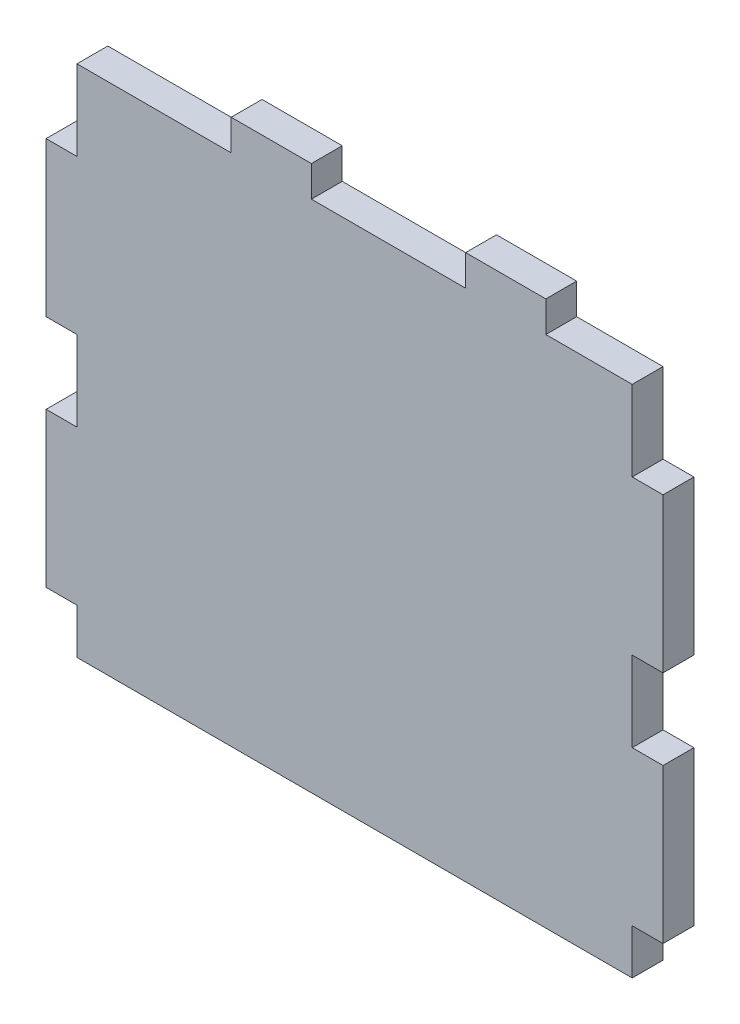
SolidWorks part; units mm, degrees
material "Oak"
ref_plane "Front Plane" through (0, 0, 0) normal (0, 0, 1) x (1, 0, 0)
ref_plane "Top Plane" through (0, 0, 0) normal (0, 1, 0) x (1, 0, 0)
ref_plane "Right Plane" through (0, 0, 0) normal (1, 0, 0) x (0, 0, -1)
sketch "Sketch1" plane through (0, 0, 0) normal (0, 0, 1) x (1, 0, 0)
  line L1 (-40.9935, 16.542) -> (19.0065, 16.542)
  line L2 (-40.9935, 16.542) -> (-40.9935, -33.458)
  line L3 (-40.9935, -33.458) -> (19.0065, -33.458)
  line L4 (19.0065, 16.542) -> (19.0065, -33.458)
  dimension "D1" = 50
  dimension "D2" = 60
extrude "Boss-Extrude1" add sketch "Sketch1" along normal blind 3
sketch "Sketch2" plane through (0, 0, 3) normal (0, 0, 1) x (1, 0, 0)
  line L12 (-40.9935, 16.542) -> (-37.9935, 16.542)
  line L13 (-40.9935, 16.542) -> (-40.9935, 8.742)
  line L14 (-40.9935, 8.742) -> (-37.9935, 8.742)
  line L15 (-37.9935, 16.542) -> (-37.9935, 8.742)
  dimension "D1" = 7.8
  dimension "D2" = 3
extrude "Cut-Extrude1" cut sketch "Sketch2" against normal through all
pattern_linear "LPattern1" count 3 spacing 22.8 along (0, -1, 0) of "Cut-Extrude1"
sketch "Sketch3" plane through (0, 0, 3) normal (0, 0, 1) x (1, 0, 0)
  line L0 (19.0065, 16.542) -> (-37.9935, 16.542) construction
  line L1 (16.0065, 16.542) -> (19.0065, 16.542)
  line L2 (16.0065, 16.542) -> (16.0065, 8.742)
  line L3 (16.0065, 8.742) -> (19.0065, 8.742)
  line L4 (19.0065, 16.542) -> (19.0065, 8.742)
  line L5 (19.0065, -33.458) -> (19.0065, 16.542) construction
  point P8 (17.5065, 16.542)
  dimension "D1" = 7.8
  dimension "D2" = 3
extrude "Cut-Extrude2" cut sketch "Sketch3" against normal through all
pattern_linear "LPattern2" count 4 spacing 22.8 along (0, -1, 0) of "Cut-Extrude2"
sketch "Sketch6" plane through (0, 0, 3) normal (0, 0, 1) x (1, 0, 0)
  line L0 (-37.9935, -33.458) -> (16.0065, -33.458) construction
  line L1 (-40.9935, -14.058) -> (-37.9935, -14.058)
  line L2 (-40.9935, -14.058) -> (-40.9935, -33.458)
  line L3 (-40.9935, -33.458) -> (-37.9935, -33.458)
  line L4 (-37.9935, -14.058) -> (-37.9935, -33.458)
  dimension "D1" = 3
extrude "Cut-Extrude3" cut sketch "Sketch6" against normal blind 10
sketch "Sketch7" plane through (0, 16.542, 0) normal (0, 1, 0) x (1, 0, 0)
  line L0 (16.0065, 0) -> (-37.9935, 0) construction
  line L1 (-22.9935, 0) -> (-15.1935, 0)
  line L2 (-22.9935, 0) -> (-22.9935, -3)
  line L3 (-22.9935, -3) -> (-15.1935, -3)
  line L4 (-15.1935, 0) -> (-15.1935, -3)
  line L5 (16.0065, -3) -> (-37.9935, -3) construction
  line L6 (-37.9935, 0) -> (-37.9935, -3) construction
  dimension "D1" = 15
  dimension "D2" = 7.8
extrude "Boss-Extrude2" add sketch "Sketch7" along normal blind 3
pattern_linear "LPattern3" count 2 spacing 22.8 along (1, 0, 0) of "Boss-Extrude2"
sketch "Sketch8" plane through (-37.9935, 0, 0) normal (-1, 0, 0) x (0, 0, 1)
  line L0 (0, -33.458) -> (0, -6.258) construction
  line L1 (0, -14.058) -> (3, -14.058)
  line L2 (0, -14.058) -> (0, -29.058)
  line L3 (0, -29.058) -> (3, -29.058)
  line L4 (3, -14.058) -> (3, -29.058)
  line L5 (3, -33.458) -> (3, -6.258) construction
  line L6 (0, -6.258) -> (3, -6.258) construction
  dimension "D1" = 7.8
  dimension "D2" = 15
extrude "Boss-Extrude3" add sketch "Sketch8" along normal blind 3
